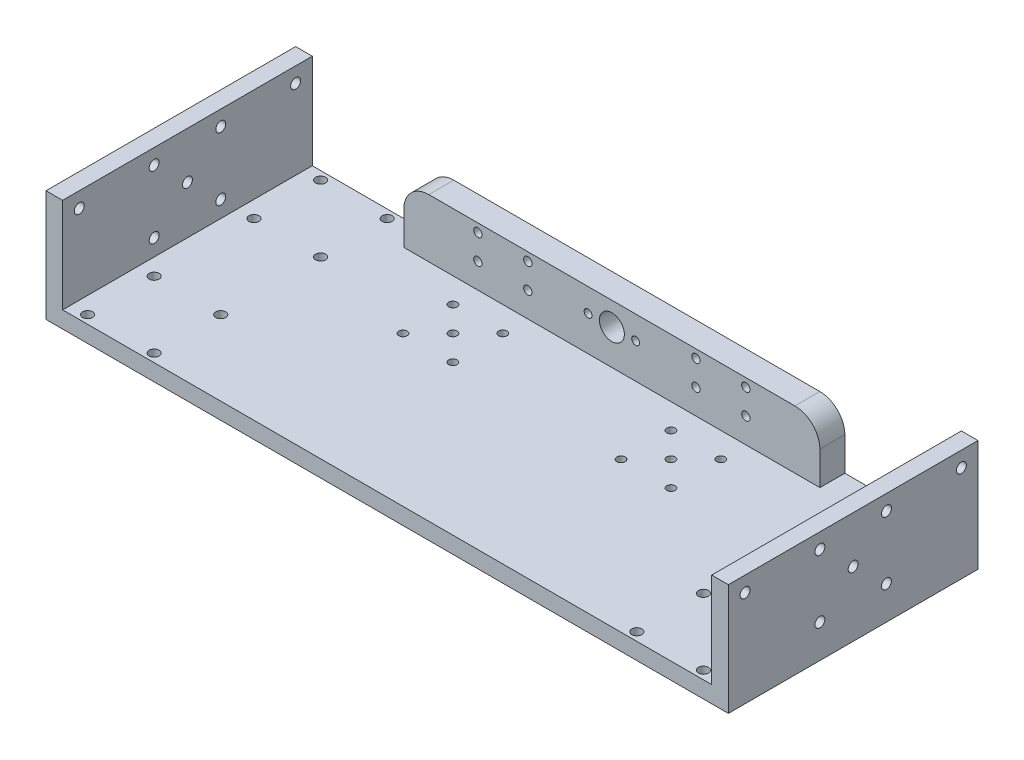
SolidWorks part; units mm, degrees
ref_plane "Front Plane" through (0, 0, 0) normal (0, 0, 1) x (1, 0, 0)
ref_plane "Top Plane" through (0, 0, 0) normal (0, 1, 0) x (1, 0, 0)
ref_plane "Right Plane" through (0, 0, 0) normal (1, 0, 0) x (0, 0, -1)
sketch "Sketch1" plane through (0, 0, 0) normal (0, 1, 0) x (1, 0, 0)
  line L1 (0, 0) -> (430, 0)
  line L2 (0, 0) -> (0, 150)
  line L3 (0, 150) -> (430, 150)
  line L4 (430, 0) -> (430, 150)
  line L5 (10, 150) -> (10, 0)
  line L7 (420, 150) -> (420, 0)
  circle A0 centre (30, 145) radius 3
  circle A1 centre (70, 145) radius 3
  circle A2 centre (70, 105) radius 3
  circle A3 centre (30, 105) radius 3
  circle A4 centre (70, 45) radius 3
  circle A5 centre (30, 45) radius 3
  circle A6 centre (70, 5) radius 3
  circle A7 centre (30, 5) radius 3
  circle A8 centre (360, 145) radius 3
  circle A9 centre (400, 145) radius 3
  circle A10 centre (360, 105) radius 3
  circle A11 centre (400, 105) radius 3
  circle A12 centre (360, 45) radius 3
  circle A13 centre (400, 45) radius 3
  circle A14 centre (360, 5) radius 3
  circle A15 centre (400, 5) radius 3
  dimension "D1" = 430
  dimension "D2" = 150
extrude "Boss-Extrude1" add sketch "Sketch1" along normal blind 10 contours L7 L3 L5 L1 A15 A14 A13 A12 A11 A10 A9 A8 A7 A6 A5 A4 A3 A2 A1 A0
sketch "Sketch2" plane through (0, 10, 0) normal (0, 1, 0) x (1, 0, 0)
  line L0 (10, 150) -> (420, 150) construction
  line L1 (10, 0) -> (20, 0)
  line L2 (10, 0) -> (10, 150)
  line L3 (10, 150) -> (20, 150)
  line L4 (20, 0) -> (20, 150)
  line L6 (420, 0) -> (410, 0)
  line L7 (420, 0) -> (420, 150)
  line L8 (420, 150) -> (410, 150)
  line L9 (410, 0) -> (410, 150)
  dimension "D1" = 10
  dimension "D2" = 10
extrude "Boss-Extrude3" add sketch "Sketch2" along normal blind 60
sketch "Sketch3" plane through (0, 10, 0) normal (0, 1, 0) x (1, 0, 0)
  line L0 (20, 150) -> (90, 150)
  line L1 (20, 150) -> (410, 150) construction
  line L2 (410, 150) -> (340, 150)
  line L4 (90, 150) -> (340, 150)
  line L5 (90, 150) -> (90, 140)
  line L6 (90, 140) -> (340, 140)
  line L7 (340, 150) -> (340, 140)
  line M19 (410, 150) -> (20, 150)
  dimension "D1" = 10
extrude "Boss-Extrude4" add sketch "Sketch3" along normal blind 60 contours L7 L5 L6 M19
fillet "Fillet2" radius 25 2 edges at (340, 70, -145) (90, 70, -145)
sketch "Sketch4" plane through (0, 0, -140) normal (0, 0, 1) x (1, 0, 0)
  line L0 (215, 10) -> (215, 31)
  line L1 (90, 10) -> (340, 10) construction
  circle A0 centre (215, 31) radius 7.5
  dimension "D1" = 15
extrude "Cut-Extrude1" cut sketch "Sketch4" against normal blind 60
sketch "Sketch5" plane through (420, 0, 0) normal (1, 0, 0) x (0, 0, -1)
  line L0 (0, 0) -> (55, 0)
  line L1 (150, 0) -> (0, 0) construction
  line L2 (150, 0) -> (95, 0)
  circle A0 centre (55, 57.8285) radius 3
  circle A1 centre (95, 57.8285) radius 3
  circle A2 centre (130, 57.8285) radius 3
  circle A3 centre (95, 20) radius 3
  circle A4 centre (55, 20) radius 3
  circle A5 centre (75, 38.9143) radius 3
  circle A6 centre (10, 57.8285) radius 3
extrude "Cut-Extrude2" cut sketch "Sketch5" against normal blind 500 contours A6 | A0 | A1 | A2 | A5 | A3 | A4
sketch "Sketch6" plane through (420, 0, 0) normal (1, 0, 0) x (0, 0, -1)
  circle A0 centre (140, 57.8285) radius 3
extrude "Cut-Extrude3" cut sketch "Sketch6" against normal blind 10
sketch "Sketch7" plane through (420, 0, 0) normal (1, 0, 0) x (0, 0, -1)
  circle A0 centre (130, 57.8285) radius 3
extrude "Boss-Extrude5" add sketch "Sketch7" against normal blind 10
sketch "Sketch8" plane through (10, 0, 0) normal (-1, 0, 0) x (0, 0, 1)
  line L0 (-95, 57.8285) -> (-140, 57.8285)
  circle A0 centre (-140, 57.8285) radius 3
extrude "Cut-Extrude4" cut sketch "Sketch8" against normal blind 10
sketch "Sketch9" plane through (10, 0, 0) normal (-1, 0, 0) x (0, 0, 1)
  circle A0 centre (-130, 57.8285) radius 3
extrude "Boss-Extrude6" add sketch "Sketch9" against normal blind 10
sketch "Sketch10" plane through (10, 0, 0) normal (-1, 0, 0) x (0, 0, 1)
  line L0 (0, 70) -> (0, 0) construction
  line L1 (-150, 70) -> (0, 70)
  line L2 (-150, 70) -> (-150, 67)
  line L3 (-150, 67) -> (0, 67)
  line L4 (0, 70) -> (0, 67)
  dimension "D1" = 3
extrude "Cut-Extrude5" cut sketch "Sketch10" against normal blind 600
sketch "Sketch11" plane through (0, 0, -140) normal (0, 0, 1) x (1, 0, 0)
  circle A0 centre (200.72, 31) radius 2.5
  circle A1 centre (229.28, 31) radius 2.5
extrude "Cut-Extrude6" cut sketch "Sketch11" against normal through all
sketch "Sketch12" plane through (0, 0, -140) normal (0, 0, 1) x (1, 0, 0)
  line L0 (215, 10) -> (149.5, 10)
  line L1 (90, 10) -> (340, 10) construction
  line L2 (20, 10) -> (410, 10) construction
  line L3 (215, 10) -> (255.5, 10)
  line L4 (149.5, 10) -> (174.5, 10)
  line L5 (149.5, 10) -> (124.5, 10)
  line L6 (280.5, 10) -> (305.5, 10)
  circle A0 centre (134.5, 55) radius 2.5
  circle A1 centre (164.5, 55) radius 2.5
  circle A2 centre (134.5, 25) radius 2.5
  circle A3 centre (164.5, 25) radius 2.5
  circle A4 centre (149.5, 40) radius 2.5
  circle A5 centre (280.5, 40) radius 2.5
  circle A6 centre (265.5, 55) radius 2.5
  circle A7 centre (295.5, 55) radius 2.5
  circle A8 centre (295.5, 25) radius 2.5
  circle A9 centre (265.5, 25) radius 2.5
  dimension "D1" = 25
  dimension "D2" = 25
extrude "Cut-Extrude7" cut sketch "Sketch12" against normal blind 10 contours A0 | A1 | A4 | A2 | A3 | A6 | A7 | A5 | A8 | A9
sketch "Sketch14" plane through (0, 10, 0) normal (0, 1, 0) x (1, 0, 0)
  line L0 (90, 140) -> (134.5, 140)
  line L1 (90, 140) -> (340, 140) construction
  line L11 (340, 140) -> (295.5, 140)
  circle A0 centre (144.5, 125) radius 2.5
  circle A1 centre (174.5, 125) radius 2.5
  circle A2 centre (144.5, 95) radius 2.5
  circle A3 centre (159.5, 110) radius 2.5
  circle A4 centre (174.5, 95) radius 2.5
  circle A5 centre (255.5, 125) radius 2.5
  circle A6 centre (285.5, 125) radius 2.5
  circle A7 centre (270.5, 110) radius 2.5
  circle A8 centre (255.5, 95) radius 2.5
  circle A9 centre (285.5, 95) radius 2.5
extrude "Cut-Extrude8" cut sketch "Sketch14" against normal blind 10 contours A0 | A1 | A3 | A4 | A2 | A5 | A6 | A7 | A8 | A9
sketch "Sketch16" plane through (0, 10, 0) normal (0, 1, 0) x (1, 0, 0)
  line L0 (144.5, 125) -> (134.5, 125)
  line L1 (174.5, 125) -> (164.5, 125)
  line L2 (159.5, 110) -> (149.5, 110)
  line L3 (144.5, 95) -> (134.5, 95)
  line L4 (174.5, 95) -> (164.5, 95)
  line L5 (285.5, 125) -> (295.5, 125)
  line L6 (255.5, 125) -> (265.5, 125)
  line L7 (270.5, 110) -> (280.5, 110)
  line L8 (285.5, 95) -> (295.5, 95)
  line L9 (255.5, 95) -> (265.5, 95)
  circle A0 centre (174.5, 125) radius 2.5
  circle A1 centre (164.5, 125) radius 2.5
  circle A2 centre (149.5, 110) radius 2.5
  circle A3 centre (164.5, 95) radius 2.5
  circle A4 centre (134.5, 95) radius 2.5
  circle A5 centre (134.5, 125) radius 2.5
  circle A6 centre (265.5, 125) radius 2.5
  circle A7 centre (280.5, 110) radius 2.5
  circle A8 centre (295.5, 125) radius 2.5
  circle A9 centre (265.5, 95) radius 2.5
  circle A10 centre (295.5, 95) radius 2.5
extrude "Cut-Extrude9" cut sketch "Sketch16" against normal blind 10
sketch "Sketch17" plane through (0, 10, 0) normal (0, 1, 0) x (1, 0, 0)
  circle A0 centre (144.5, 125) radius 2.5
  circle A1 centre (174.5, 125) radius 2.5
  circle A2 centre (159.5, 110) radius 2.5
  circle A3 centre (144.5, 95) radius 2.5
  circle A4 centre (174.5, 95) radius 2.5
  circle A5 centre (285.5, 125) radius 2.5
  circle A6 centre (255.5, 125) radius 2.5
  circle A7 centre (270.5, 110) radius 2.5
  circle A8 centre (255.5, 95) radius 2.5
  circle A9 centre (285.5, 95) radius 2.5
extrude "Boss-Extrude7" add sketch "Sketch17" against normal blind 10
sketch "Sketch18" plane through (0, 0, -150) normal (0, 0, -1) x (-1, 0, 0)
  line L0 (-340, 10) -> (-410, 10)
  line L1 (-410, 10) -> (-410, 67)
  line L2 (-410, 67) -> (-420, 67)
  line L3 (-420, 67) -> (-420, 0)
  line L4 (-420, 0) -> (-10, 0)
  line L5 (-10, 0) -> (-10, 67)
  line L6 (-10, 67) -> (-20, 67)
  line L7 (-20, 67) -> (-20, 10)
  line L8 (-20, 67) -> (-20, 10) construction
  line L9 (-20, 10) -> (-90, 10)
  line L10 (-90, 10) -> (-90, 67)
  line L11 (-90, 67) -> (-340, 67)
  line L12 (-340, 67) -> (-340, 10)
  circle A0 centre (-295.5, 55) radius 2.5
  circle A1 centre (-280.5, 40) radius 2.5
  circle A2 centre (-265.5, 55) radius 2.5
  circle A3 centre (-295.5, 25) radius 2.5
  circle A4 centre (-265.5, 25) radius 2.5
  circle A5 centre (-229.28, 31) radius 2.5
  circle A6 centre (-215, 31) radius 7.5
  circle A7 centre (-200.72, 31) radius 2.5
  circle A8 centre (-164.5, 55) radius 2.5
  circle A9 centre (-134.5, 55) radius 2.5
  circle A10 centre (-149.5, 40) radius 2.5
  circle A11 centre (-134.5, 25) radius 2.5
  circle A12 centre (-164.5, 25) radius 2.5
extrude "Boss-Extrude8" add sketch "Sketch18" along normal blind 5
fillet "Fillet3" radius 22 1 edges at (340, 67, -152.5)
fillet "Fillet4" radius 22 1 edges at (90, 67, -152.5)
sketch "Sketch19" plane through (0, 0, 0) normal (0, 0, 1) x (1, 0, 0)
  line L0 (10, 67) -> (20, 67)
  line L1 (20, 67) -> (20, 10)
  line L2 (20, 10) -> (410, 10)
  line L3 (410, 10) -> (410, 67)
  line L4 (410, 67) -> (420, 67)
  line L5 (420, 67) -> (420, 0)
  line L6 (420, 0) -> (10, 0)
  line L7 (10, 0) -> (10, 67)
extrude "Boss-Extrude9" add sketch "Sketch19" along normal blind 5
sketch "Sketch20" plane through (0, 0, 5) normal (0, 0, 1) x (1, 0, 0)
  line L0 (10, 67) -> (20, 67)
  line L1 (20, 67) -> (20, 10)
  line L2 (20, 10) -> (410, 10)
  line L3 (410, 10) -> (410, 67)
  line L4 (410, 67) -> (420, 67)
  line L5 (420, 67) -> (420, 0)
  line L6 (420, 0) -> (10, 0)
  line L7 (10, 0) -> (10, 67)
extrude "Cut-Extrude11" cut sketch "Sketch20" against normal blind 5
sketch "Sketch21" plane through (0, 0, -155) normal (0, 0, -1) x (-1, 0, 0)
  line L0 (-420, 67) -> (-410, 67)
  line L1 (-410, 67) -> (-420, 67) construction
  line L2 (-410, 10) -> (-410, 67) construction
  line L3 (-410, 67) -> (-410, 10)
  line L4 (-410, 10) -> (-340, 10)
  line L5 (-340, 10) -> (-340, 67)
  line L6 (-340, 67) -> (-90, 67)
  line L7 (-90, 67) -> (-90, 10)
  line L8 (-90, 10) -> (-20, 10)
  line L9 (-20, 10) -> (-20, 67)
  line L10 (-20, 67) -> (-10, 67)
  line L11 (-10, 67) -> (-10, 0)
  line L12 (-10, 0) -> (-420, 0)
  line L13 (-420, 0) -> (-420, 67)
  circle A0 centre (-295.5, 55) radius 2.5
  circle A1 centre (-265.5, 55) radius 2.5
  circle A2 centre (-215, 31) radius 7.5
  circle A3 centre (-200.72, 31) radius 2.5
  circle A4 centre (-229.28, 31) radius 2.5
  circle A5 centre (-265.5, 25) radius 2.5
  circle A6 centre (-280.5, 40) radius 2.5
  circle A7 centre (-295.5, 25) radius 2.5
  circle A8 centre (-164.5, 55) radius 2.5
  circle A9 centre (-149.5, 40) radius 2.5
  circle A10 centre (-164.5, 25) radius 2.5
  circle A11 centre (-134.5, 25) radius 2.5
  circle A12 centre (-134.5, 55) radius 2.5
extrude "Cut-Extrude12" cut sketch "Sketch21" against normal blind 5
sketch "Sketch22" plane through (0, 0, -140) normal (0, 0, 1) x (1, 0, 0)
  line L0 (90, 10) -> (90, 67)
  line L1 (90, 67) -> (340, 67)
  line L2 (340, 67) -> (340, 10)
  line L3 (340, 10) -> (90, 10)
  circle A0 centre (134.5, 55) radius 2.5
  circle A1 centre (164.5, 55) radius 2.5
  circle A2 centre (149.5, 40) radius 2.5
  circle A3 centre (164.5, 25) radius 2.5
  circle A4 centre (134.5, 25) radius 2.5
  circle A5 centre (215, 31) radius 7.5
  circle A6 centre (229.28, 31) radius 2.5
  circle A7 centre (200.72, 31) radius 2.5
  circle A8 centre (265.5, 55) radius 2.5
  circle A9 centre (280.5, 40) radius 2.5
  circle A10 centre (295.5, 55) radius 2.5
  circle A11 centre (295.5, 25) radius 2.5
  circle A12 centre (265.5, 25) radius 2.5
extrude "Boss-Extrude10" add sketch "Sketch22" along normal blind 5
fillet "Fillet5" radius 22 2 edges at (90, 67, -137.5) (340, 67, -137.5)
sketch "Sketch23" plane through (0, 10, 0) normal (0, 1, 0) x (1, 0, 0)
  line L0 (134.5, 125) -> (134.5, 120)
  line L1 (164.5, 125) -> (164.5, 120)
  line L2 (149.5, 110) -> (149.5, 105)
  line L3 (164.5, 95) -> (164.5, 90)
  line L4 (134.5, 95) -> (134.5, 90)
  line L5 (265.5, 125) -> (265.5, 120)
  line L6 (295.5, 125) -> (295.5, 120)
  line L7 (280.5, 110) -> (280.5, 105)
  line L8 (265.5, 95) -> (265.5, 90)
  line L9 (295.5, 95) -> (295.5, 90)
  circle A0 centre (265.5, 120) radius 2.5
  circle A1 centre (295.5, 120) radius 2.5
  circle A2 centre (280.5, 105) radius 2.5
  circle A3 centre (295.5, 90) radius 2.5
  circle A4 centre (265.5, 90) radius 2.5
  circle A5 centre (164.5, 120) radius 2.5
  circle A6 centre (134.5, 120) radius 2.5
  circle A7 centre (149.5, 105) radius 2.5
  circle A8 centre (164.5, 90) radius 2.5
  circle A9 centre (134.5, 90) radius 2.5
extrude "Boss-Extrude12" add sketch "Sketch23" along normal blind 5
sketch "Sketch24" plane through (0, 10, 0) normal (0, 1, 0) x (1, 0, 0)
  circle A0 centre (295.5, 125) radius 2.5
  circle A1 centre (265.5, 125) radius 2.5
  circle A2 centre (280.5, 110) radius 2.5
  circle A3 centre (295.5, 95) radius 2.5
  circle A4 centre (265.5, 95) radius 2.5
  circle A5 centre (164.5, 125) radius 2.5
  circle A6 centre (134.5, 125) radius 2.5
  circle A7 centre (149.5, 110) radius 2.5
  circle A8 centre (164.5, 95) radius 2.5
  circle A9 centre (134.5, 95) radius 2.5
extrude "Boss-Extrude13" add sketch "Sketch24" against normal blind 10
sketch "Sketch25" plane through (0, 10, 0) normal (0, 1, 0) x (1, 0, 0)
  circle A0 centre (134.5, 120) radius 2.5
  circle A1 centre (164.5, 120) radius 2.5
  circle A2 centre (149.5, 105) radius 2.5
  circle A3 centre (164.5, 90) radius 2.5
  circle A4 centre (134.5, 90) radius 2.5
  circle A5 centre (265.5, 120) radius 2.5
  circle A6 centre (295.5, 120) radius 2.5
  circle A7 centre (280.5, 105) radius 2.5
  circle A8 centre (295.5, 90) radius 2.5
  circle A9 centre (265.5, 90) radius 2.5
extrude "Cut-Extrude19" cut sketch "Sketch25" against normal blind 10
sketch "Sketch27" plane through (0, 67, 0) normal (0, 1, 0) x (1, 0, 0)
  line L1 (90, 150) -> (340, 150)
  line L2 (90, 150) -> (90, 135)
  line L3 (90, 135) -> (340, 135)
  line L4 (340, 150) -> (340, 135)
extrude "Cut-Extrude20" cut sketch "Sketch27" against normal blind 22
sketch "Sketch28" plane through (0, 0, -135) normal (0, 0, 1) x (1, 0, 0)
  line L0 (149.5, 40) -> (134.5, 40)
  line L1 (149.5, 40) -> (164.5, 40)
  line L2 (280.5, 40) -> (265.5, 40)
  line L3 (280.5, 40) -> (295.5, 40)
  circle A0 centre (265.5, 40) radius 2.5
  circle A1 centre (295.5, 40) radius 2.5
  circle A2 centre (134.5, 40) radius 2.5
  circle A3 centre (164.5, 40) radius 2.5
extrude "Cut-Extrude21" cut sketch "Sketch28" against normal blind 22
sketch "Sketch29" plane through (0, 0, -135) normal (0, 0, 1) x (1, 0, 0)
  circle A0 centre (280.5, 40) radius 2.5
  circle A1 centre (149.5, 40) radius 2.5
fillet "Fillet6" radius 15 1 edges
fillet "Fillet7" radius 15 1 edges
sketch "Sketch30" plane through (0, 0, -135) normal (0, 0, 1) x (1, 0, 0)
  circle A0 centre (200.72, 31) radius 2.34
  circle A1 centre (229.28, 31) radius 2.34
  circle A2 centre (200.72, 31) radius 2.5
  circle A3 centre (229.28, 31) radius 2.5
  dimension "D1" = 4.68
  dimension "D2" = 4.68
extrude "Boss-Extrude15" add sketch "Sketch30" against normal through all
sketch "Sketch32" plane through (0, 0, -135) normal (0, 0, 1) x (1, 0, 0)
  circle A0 centre (149.5, 40) radius 2.5
  circle A1 centre (280.5, 40) radius 2.5
extrude "Boss-Extrude17" add sketch "Sketch32" against normal through all
